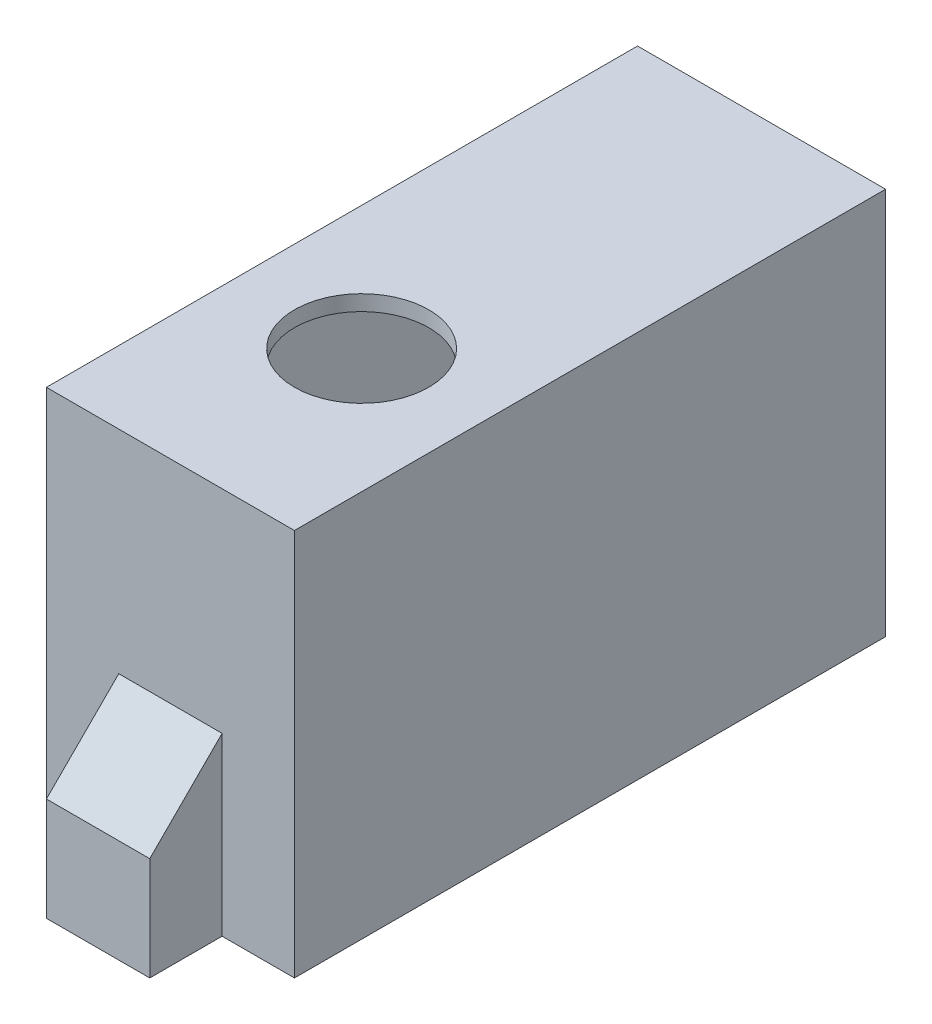
SolidWorks part; units mm, degrees
ref_plane "Front Plane" through (0, 0, 0) normal (0, 0, 1) x (1, 0, 0)
ref_plane "Top Plane" through (0, 0, 0) normal (0, 1, 0) x (1, 0, 0)
ref_plane "Right Plane" through (0, 0, 0) normal (1, 0, 0) x (0, 0, -1)
sketch "Sketch1" plane through (0, 0, 0) normal (0, 1, 0) x (1, 0, 0)
  line L1 (-10, 26.6) -> (10, 26.6)
  line L2 (-10, 26.6) -> (-10, -26.6)
  line L3 (-10, -26.6) -> (10, -26.6)
  line L4 (10, 26.6) -> (10, -26.6)
  dimension "D1" = 20
  dimension "D2" = 53.2
  dimension "D3" = 10
  dimension "D4" = 26.6
extrude "Boss-Extrude1" add sketch "Sketch1" along normal blind 36
shell "Shell1" thickness 2 removed face at (0, 0, 0) outward yes
sketch "Sketch2" plane through (0, 38, 0) normal (0, 1, 0) x (1, 0, 0)
  line L0 (-12, -28.6) -> (12, -28.6) construction
  circle A0 centre (0, -10.1) radius 6.5
  dimension "D1" = 18.5
extrude "Cut-Extrude1" cut sketch "Sketch2" against normal blind 5
sketch "Sketch3" plane through (0, 0, -28.6) normal (0, 0, -1) x (-1, 0, 0)
  line L0 (-12, 0) -> (12, 0) construction
  line L1 (-5, 10) -> (5, 10)
  line L2 (-5, 10) -> (-5, 0)
  line L3 (-5, 0) -> (5, 0)
  line L4 (5, 10) -> (5, 0)
  line L5 (-12, 38) -> (-12, 0) construction
  dimension "D1" = 10
  dimension "D2" = 7
  dimension "D3" = 10
extrude "Boss-Extrude2" add sketch "Sketch3" along normal blind 7
sketch "Sketch4" plane through (0, 0, 28.6) normal (0, 0, 1) x (1, 0, 0)
  line L0 (-12, 0) -> (12, 0) construction
  line L1 (-5, 0) -> (5, 0)
  line L2 (-5, 0) -> (-5, 10)
  line L3 (-5, 10) -> (5, 10)
  line L4 (5, 0) -> (5, 10)
  line L5 (-12, 38) -> (-12, 0) construction
  dimension "D1" = 7
  dimension "D2" = 10
  dimension "D3" = 10
extrude "Boss-Extrude3" add sketch "Sketch4" along normal blind 7
sketch "Sketch5" plane through (0, 0, 0) normal (0, -1, 0) x (1, 0, 0)
  line L0 (-5, 35.6) -> (5, 35.6) construction
  line L1 (5, -35.6) -> (-5, -35.6) construction
  circle A0 centre (0, 31.6) radius 1.75
  circle A1 centre (0, -31.6) radius 1.75
  dimension "D1" = 4
  dimension "D2" = 4
extrude "Cut-Extrude2" cut sketch "Sketch5" against normal blind 7
chamfer "Chamfer1" distance 7 angle 45 2 edges at (0, 10, -28.6) (0, 10, 28.6)
sketch "Sketch6" plane through (0, 38, 0) normal (0, 1, 0) x (1, 0, 0)
  line L1 (15.0746, -31.3093) -> (-14.3394, -31.3093)
  line L2 (15.0746, -31.3093) -> (15.0746, 30.8054)
  line L3 (15.0746, 30.8054) -> (-14.3394, 30.8054)
  line L4 (-14.3394, -31.3093) -> (-14.3394, 30.8054)
extrude "Cut-Extrude3" cut sketch "Sketch6" against normal blind 0.5
